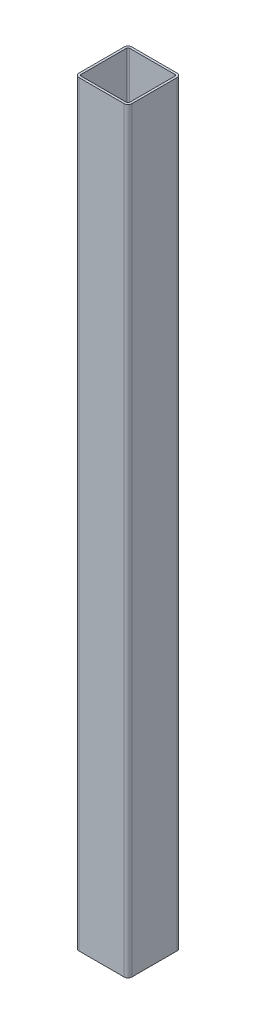
SolidWorks part; units mm, degrees
ref_plane "Спереди" through (0, 0, 0) normal (0, 0, 1) x (1, 0, 0)
ref_plane "Сверху" through (0, 0, 0) normal (0, 1, 0) x (1, 0, 0)
ref_plane "Справа" through (0, 0, 0) normal (1, 0, 0) x (0, 0, -1)
sketch "Эскиз1" plane through (0, 0, 0) normal (0, 1, 0) x (1, 0, 0)
  line L1 (-30, 35) -> (30, 35)
  line L2 (-35, 30) -> (-35, -30)
  line L3 (-30, -35) -> (30, -35)
  line L4 (35, 30) -> (35, -30)
  line L5 (-35, 35) -> (35, -35) construction
  line L6 (-35, -35) -> (35, 35) construction
  arc A0 (30, -35) -> (35, -30) centre (30, -30) ccw
  arc A1 (30, 35) -> (35, 30) centre (30, 30) cw
  arc A2 (-30, 35) -> (-35, 30) centre (-30, 30) ccw
  arc A3 (-35, -30) -> (-30, -35) centre (-30, -30) ccw
  point P0 (0, 0)
  dimension "D1" = 5
extrude "Вытянуть-Тонкостенный1" add sketch "Эскиз1" along normal blind 1000 thin thin type one direction reverse wall 3
ref_axis "Ось1" through (0, -50, 0) along (0, 1, 0)
